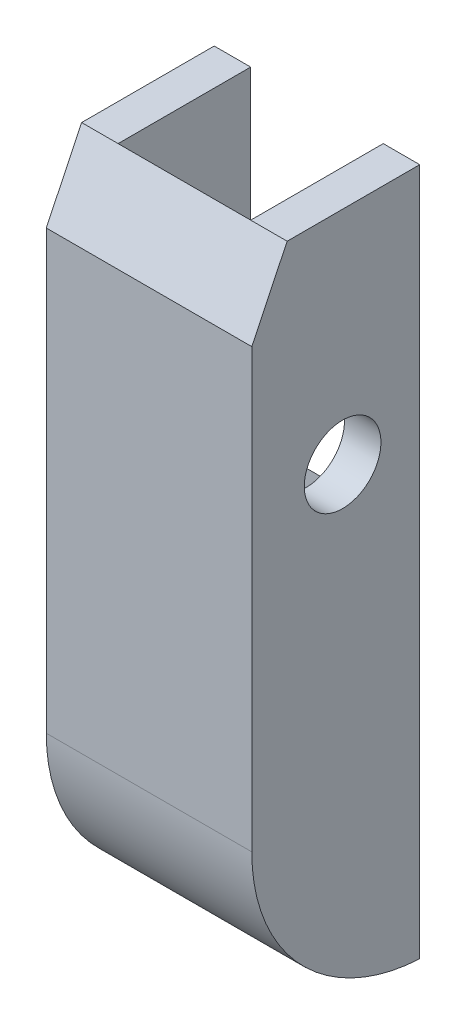
SolidWorks part; units mm, degrees
ref_plane "Front Plane" through (0, 0, 0) normal (0, 0, 1) x (1, 0, 0)
ref_plane "Top Plane" through (0, 0, 0) normal (0, 1, 0) x (1, 0, 0)
ref_plane "Right Plane" through (0, 0, 0) normal (1, 0, 0) x (0, 0, -1)
sketch "Sketch1" plane through (0, 0, 0) normal (0, 0, 1) x (1, 0, 0)
  line L1 (0, 0) -> (11.811, 0)
  line L2 (0, 0) -> (0, 45.9892)
  line L3 (0, 45.9892) -> (11.811, 45.9892)
  line L4 (11.811, 0) -> (11.811, 45.9892)
  dimension "D1" = 11.811
  dimension "D2" = 45.9892
extrude "Boss-Extrude1" add sketch "Sketch1" along normal blind 9.652 contours L2 L3 L4 L1
fillet "Fillet5" radius 4.826 1 edges at (5.9055, 45.9892, 0)
sketch "Sketch2" plane through (0, 0, 0) normal (0, 0, -1) x (-1, 0, 0)
  line L0 (0, 45.9892) -> (-11.811, 45.9892) construction
  line L1 (-9.7155, 45.9892) -> (-2.0955, 45.9892)
  line L2 (-9.7155, 45.9892) -> (-9.7155, 23.6372)
  line L3 (-9.7155, 23.6372) -> (-2.0955, 23.6372)
  line L4 (-2.0955, 45.9892) -> (-2.0955, 23.6372)
  line L5 (0, 0) -> (0, 41.1632) construction
  dimension "D1" = 22.352
  dimension "D2" = 7.62
  dimension "D3" = 2.0955
extrude "Cut-Extrude1" cut sketch "Sketch2" against normal blind 7.62
sketch "Sketch3" plane through (0, 0, 0) normal (-1, 0, 0) x (0, 0, 1)
  line L0 (7.62, 45.9892) -> (7.62, 23.6372) construction
  line L2 (7.62, 23.6372) -> (0, 23.6372) construction
  circle A0 centre (4.4323, 26.8249) radius 2.2035
  dimension "D1" = 3.1877
  dimension "D3" = 4.4069
  dimension "D2" = 3.1877
extrude "Cut-Extrude2" cut sketch "Sketch3" against normal through all and the other way through all
fillet "Fillet4" radius 4.826 1 edges at (5.9055, 45.9892, 9.652)
fillet "Fillet6" radius 10.16 1 edges at (5.9055, 0, 9.652)
sketch "Sketch4" plane through (11.811, 0, 0) normal (1, 0, 0) x (0, 0, -1)
  line L0 (-9.652, 35.2938) -> (-7.62, 39.5249)
  line L1 (-9.652, 10.1473) -> (-9.652, 41.1632) construction
  line L2 (-7.62, 39.5249) -> (0, 39.5249)
  line L3 (0, 0) -> (0, 41.1632) construction
  line L4 (-9.652, 35.2938) -> (-9.652, 45.9892)
  line L5 (-9.652, 45.9892) -> (0, 45.9892)
  line L6 (0, 45.9892) -> (0, 39.5249)
  line L7 (-0.4369, 28.7437) -> (4.2626, 18.9582) construction
  line L8 (-4.4323, 26.8249) -> (0, 26.8249) construction
  line L9 (-4.4323, 26.8249) -> (-0.4369, 28.7437) construction
  line L10 (-4.4323, 26.8249) -> (-0.4369, 24.9061) construction
  arc A0 (-4.826, 45.9892) -> (-9.652, 41.1632) centre (-4.826, 41.1632) ccw construction
  circle A1 centre (7.1247, 20.3327) radius 3.175 construction
  point P14 (-4.4323, 26.8249)
  point P22 (0, 0)
  point P23 (0, 0)
  dimension "D2" = 6.35
  dimension "D1" = 12.7
  dimension "D3" = 11.557
  dimension "D4" = 6.4922
extrude "Cut-Extrude3" cut sketch "Sketch4" against normal through all
sketch "Sketch5" plane through (9.7155, 0, 0) normal (-1, 0, 0) x (0, 0, 1)
  line L0 (5.1581, 23.6372) -> (0, 21.1601)
  line L1 (0, 21.1601) -> (0, 23.6372)
  line L2 (0, 23.6372) -> (5.1581, 23.6372)
  line L3 (4.4323, 26.8249) -> (0.4369, 24.9061) construction
  line L4 (4.4323, 26.8249) -> (7.62, 26.8249) construction
  line L5 (4.4323, 26.8249) -> (5.8123, 23.9514) construction
  line L6 (7.62, 39.5249) -> (7.62, 23.6372) construction
  line L7 (5.8123, 23.9514) -> (5.1581, 23.6372)
  line L8 (7.62, 26.8249) -> (7.62, 23.6372)
  line L9 (7.62, 23.6372) -> (5.1581, 23.6372)
  arc A0 (5.8123, 23.9514) -> (7.62, 26.8249) centre (4.4323, 26.8249) ccw
  point P2 (7.62, 26.845)
  point P13 (0, 0)
  line M4 (7.62, 23.6372) -> (7.62, 39.5249)
  line M7 (0, 23.6372) -> (7.62, 23.6372)
extrude "Cut-Extrude4" cut sketch "Sketch5" along normal up to surface (7.62 mm away) contours L1 L0 M7 region at (9.7155, 22.8115, 1.7194) up to face at (2.0955, 24.6215, 4.4323)
extrude "Boss-Extrude2" add sketch "Sketch5<3>" along normal up to surface (7.62 mm away) contours A0 L7 M7 M4 region at (9.7155, 24.361, 6.9399) up to face at (2.0955, 24.6215, 4.4323)
sketch "Sketch5<3>" plane through (9.7155, 0, 0) normal (-1, 0, 0) x (0, 0, 1) same geometry as "Sketch5"
